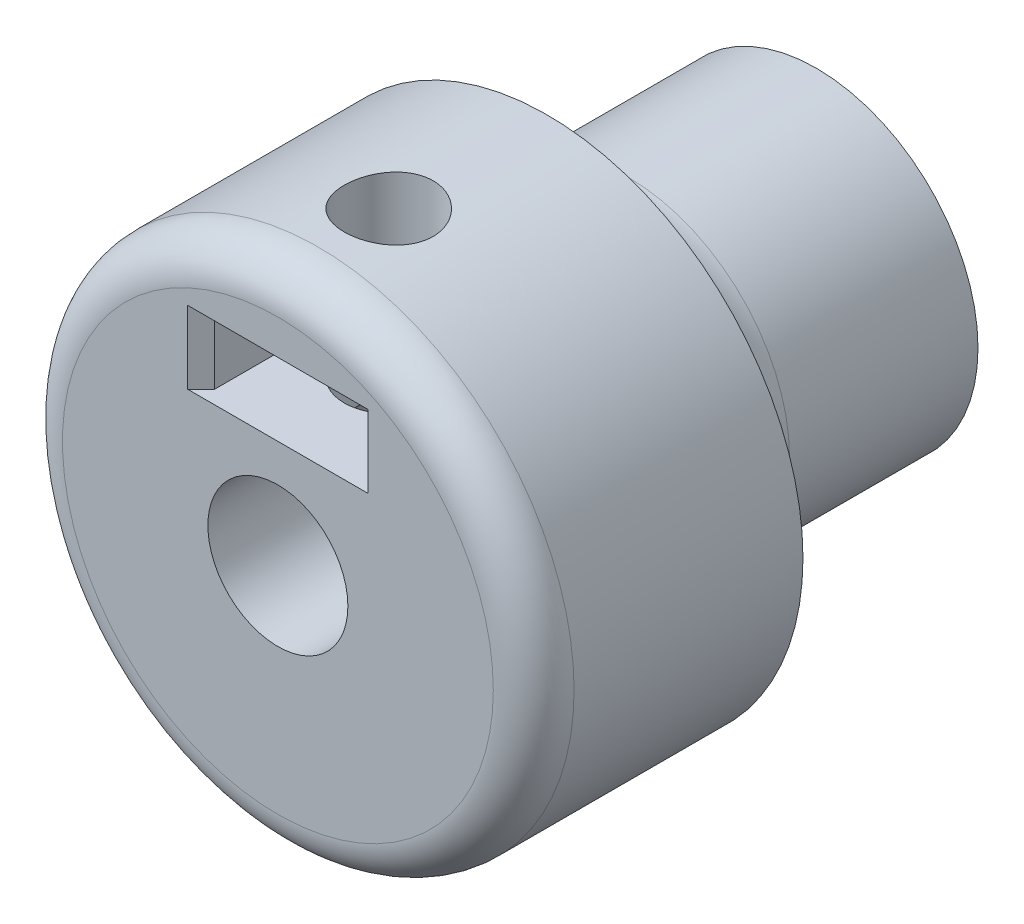
SolidWorks part; units mm, degrees
ref_plane "Front Plane" through (0, 0, 0) normal (0, 0, 1) x (1, 0, 0)
ref_plane "Top Plane" through (0, 0, 0) normal (0, 1, 0) x (1, 0, 0)
ref_plane "Right Plane" through (0, 0, 0) normal (1, 0, 0) x (0, 0, -1)
sketch "Sketch1" plane through (0, 0, 0) normal (0, 0, 1) x (1, 0, 0)
  circle A0 centre (0, 0) radius 9.5
  dimension "D1" = 19
extrude "Boss-Extrude1" add sketch "Sketch1" along normal blind 10
sketch "Sketch6" plane through (0, 0, 0) normal (0, 0, -1) x (-1, 0, 0)
  circle A0 centre (0, 0) radius 6
  dimension "D1" = 12
extrude "Boss-Extrude2" add sketch "Sketch6" along normal blind 10
sketch "Sketch2" plane through (0, 0, 10) normal (0, 0, 1) x (1, 0, 0)
  circle A0 centre (0, 0) radius 2.6
  dimension "D1" = 5.2
extrude "Cut-Extrude1" cut sketch "Sketch2" against normal blind 10
sketch "Sketch3" plane through (0, 0, 0) normal (0, 0, 1) x (1, 0, 0)
  circle A0 centre (0, 0) radius 2.15
  dimension "D1" = 4.3
extrude "Cut-Extrude2" cut sketch "Sketch3" against normal through all
ref_plane "Plane1" through (0, 0, -7) normal (0, 0, -1) x (-1, 0, 0)
sketch "Sketch4" plane through (0, 0, -7) normal (0, 0, -1) x (-1, 0, 0)
  line L0 (-3.65, -9.1053) -> (3.65, -9.1053)
  line L2 (3.65, -9.1053) -> (3.65, 2.1073)
  line L3 (3.65, 2.1073) -> (0, 4.2147)
  line L4 (0, 4.2147) -> (-3.65, 2.1073)
  line L5 (-3.65, 2.1073) -> (-3.65, -9.1053)
  line L8 (-1.825, -3.161) -> (0.9907, -4.7866) [skipped]
  line L9 (1.825, -3.161) -> (4.6407, -1.5354) [skipped]
  circle A0 centre (0, 0) radius 3.65 construction
  dimension "D1" = 7.3
extrude "Cut-Extrude3" cut sketch "Sketch4" against normal blind 3.3
ref_plane "Plane2" through (0, 4, 0) normal (0, 1, 0) x (-1, 0, 0)
sketch "Sketch5" plane through (0, 4, 0) normal (0, 1, 0) x (-1, 0, 0)
  line L0 (0, 10) -> (0, 12.4499) construction
  line L1 (9.5, 10) -> (-9.5, 10) construction
  line L2 (-2.85, 11.494) -> (2.85, 11.494)
  line L3 (0, 2.7091) -> (2.85, 4.3546)
  line L4 (2.85, 4.3546) -> (2.85, 11.494)
  line L7 (-2.85, 11.494) -> (-2.85, 4.3546)
  line L8 (-2.85, 4.3546) -> (0, 2.7091)
  line L10 (-2.4391, 10.6991) -> (-4.4269, 11.8467) [skipped]
  line L11 (2.8139, 10.9155) -> (0.8261, 9.7679) [skipped]
  circle A0 centre (0, 6) radius 2.85 construction
  dimension "D1" = 5.7
  dimension "D2" = 4
extrude "Cut-Extrude4" cut sketch "Sketch5" along normal blind 2.7
ref_plane "Plane3" through (0, 9.5, 0) normal (0, 1, 0) x (-1, 0, 0)
sketch "Sketch7" plane through (0, 9.5, 0) normal (0, 1, 0) x (-1, 0, 0)
  line L0 (-2.85, 4.3546) -> (0, 2.7091) construction
  line L1 (0, 2.7091) -> (2.85, 4.3546) construction
  circle A0 centre (0, 5.8845) radius 2.75 construction
  circle A1 centre (0, 5.8845) radius 1.65
  dimension "D1" = 5.5
  dimension "D2" = 3.3
extrude "Cut-Extrude5" cut sketch "Sketch7" against normal up to surface (6.9 mm away) up to face at (2.6, 0, 0)
fillet "Fillet1" radius 3 1 edges at (6, 0, 0)
chamfer "Chamfer1" distance 0.5 angle 45 2 edges at (3.65, -4.7621, -5.35) (-3.65, -4.7621, -5.35) first distance on face at (3.65, -1.3274, -5.35) first distance on face at (-3.65, -1.3274, -5.35)
chamfer "Chamfer2" distance 0.5 angle 45 2 edges at (2.85, 5.35, 10) (-2.85, 5.35, 10)
fillet "Fillet2" radius 1.5 1 edges at (9.5, 0, 10)
